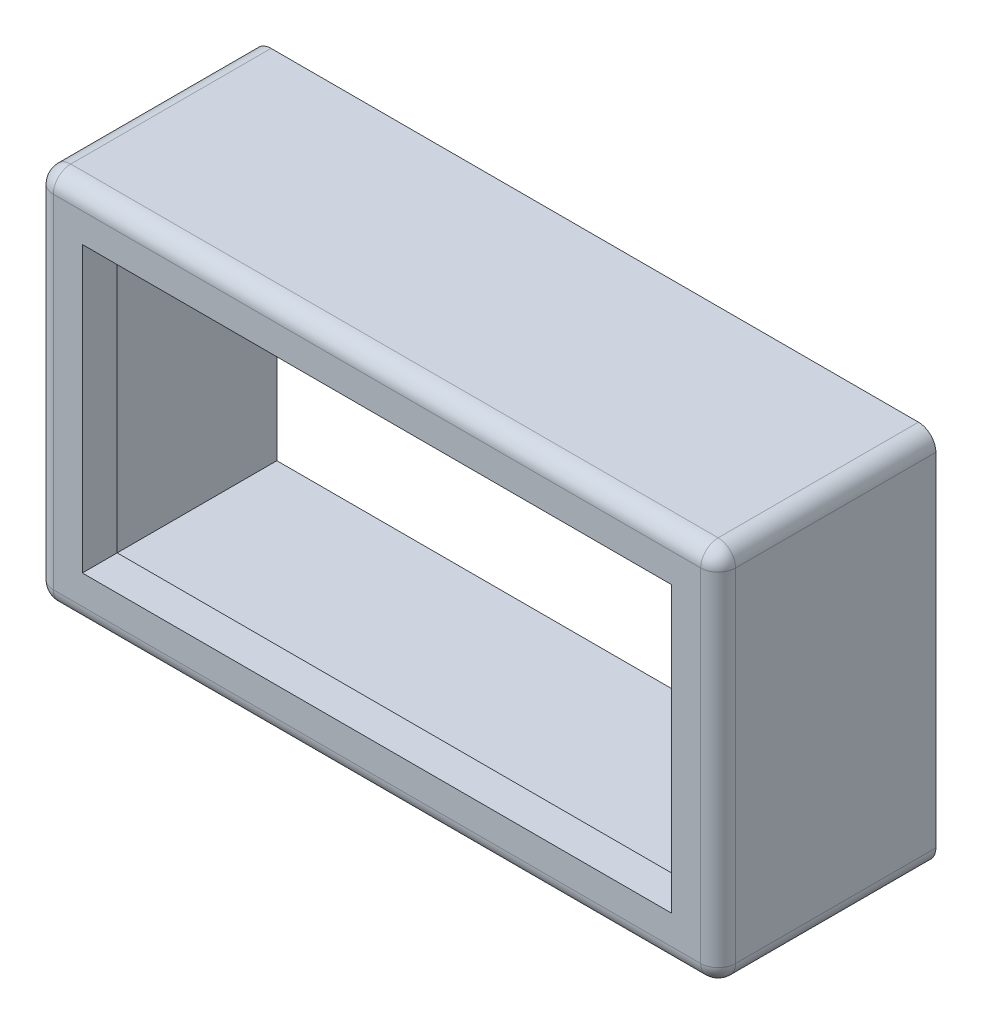
SolidWorks part; units mm, degrees
ref_plane "Front Plane" through (0, 0, 0) normal (0, 0, 1) x (1, 0, 0)
ref_plane "Top Plane" through (0, 0, 0) normal (0, 1, 0) x (1, 0, 0)
ref_plane "Right Plane" through (0, 0, 0) normal (1, 0, 0) x (0, 0, -1)
sketch "Sketch1" plane through (0, 0, 0) normal (0, 0, 1) x (1, 0, 0)
  line L4 (29.6863, -39.0525) -> (14.7638, -39.0525)
  line L5 (14.7638, -39.0525) -> (14.7638, -47.3075)
  line L6 (14.7638, -47.3075) -> (29.6863, -47.3075)
  line L7 (29.6863, -47.3075) -> (29.6863, -39.0525)
  line L8 (29.6863, -39.0525) -> (14.7638, -39.0525)
  line L9 (14.7638, -39.0525) -> (14.7638, -47.3075)
  line L10 (14.7638, -47.3075) -> (29.6863, -47.3075)
  line L11 (29.6863, -47.3075) -> (29.6863, -39.0525)
  line L12 (15.7798, -46.2915) -> (28.6703, -46.2915)
  line L13 (15.7798, -40.0685) -> (15.7798, -46.2915)
  line L14 (28.6703, -40.0685) -> (15.7798, -40.0685)
  line L15 (28.6703, -46.2915) -> (28.6703, -40.0685)
  line L16 (15.7798, -46.2915) -> (28.6703, -46.2915)
  line L17 (15.7798, -40.0685) -> (15.7798, -46.2915)
  line L18 (28.6703, -40.0685) -> (15.7798, -40.0685)
  line L19 (28.6703, -46.2915) -> (28.6703, -40.0685)
  dimension "D1" = 0
  dimension "D2" = 0
extrude "Boss-Extrude1" add sketch "Sketch1" against normal blind 4.7625
sketch "Sketch2" plane through (0, 0, -4.7625) normal (0, 0, -1) x (-1, 0, 0)
  line L0 (-15.7798, -46.2915) -> (-14.7638, -47.3075) construction
  line L1 (-28.6703, -40.0685) -> (-29.6863, -39.0525) construction
  line L3 (-29.1783, -39.5605) -> (-15.2718, -39.5605)
  line L4 (-29.1783, -39.5605) -> (-29.1783, -46.7995)
  line L5 (-29.1783, -46.7995) -> (-15.2718, -46.7995)
  line L6 (-15.2718, -39.5605) -> (-15.2718, -46.7995)
  line L7 (-29.1783, -39.5605) -> (-15.2718, -46.7995) construction
  line L8 (-29.1783, -46.7995) -> (-15.2718, -39.5605) construction
  point P12 (-22.225, -43.18)
extrude "Cut-Extrude1" cut sketch "Sketch2" against normal offset from surface (4.0005 mm away) 0.762 up to face at (22.225, -43.18, 0)
fillet "Fillet1" radius 0.381 8 edges at (29.6863, -43.18, 0) (22.225, -47.3075, 0) (14.7638, -43.18, 0) (22.225, -39.0525, 0) (29.6863, -39.0525, -2.3813) (14.7638, -47.3075, -2.3813) (29.6863, -47.3075, -2.3813) (14.7638, -39.0525, -2.3813)
